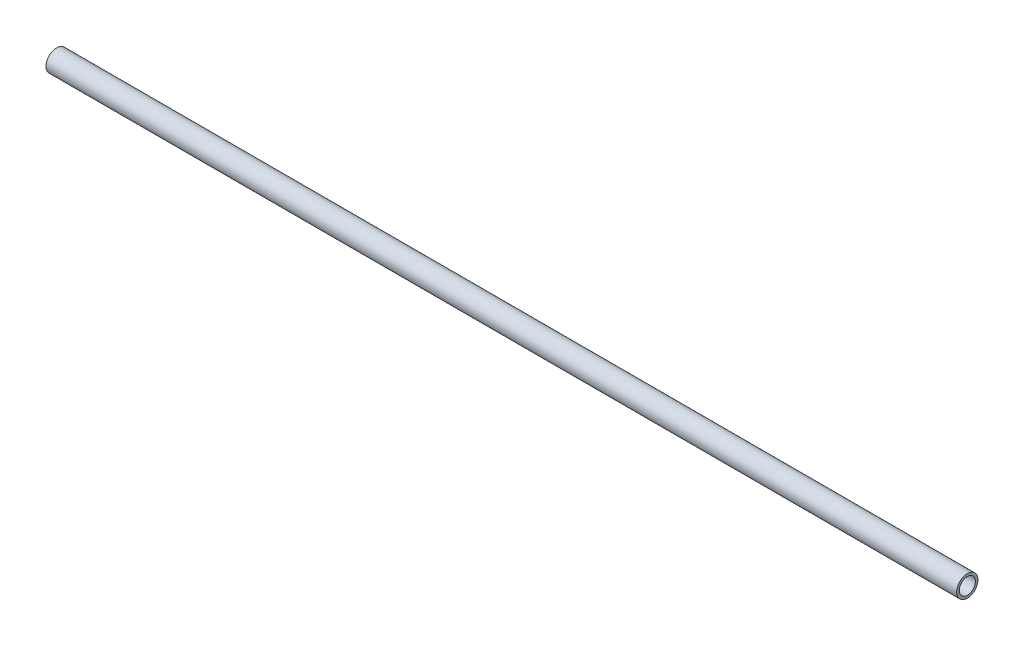
SolidWorks part; units mm, degrees
ref_plane "Front Plane" through (0, 0, 0) normal (0, 0, 1) x (1, 0, 0)
ref_plane "Top Plane" through (0, 0, 0) normal (0, 1, 0) x (1, 0, 0)
ref_plane "Right Plane" through (0, 0, 0) normal (1, 0, 0) x (0, 0, -1)
ref_axis "Axis1" through (-4.5, 0, 0) along (1, 0, 0)
sketch "Sketch1" plane through (0, 0, 0) normal (1, 0, 0) x (0, 0, -1)
  circle A0 centre (0, 0) radius 0.8001
  circle A1 centre (0, 0) radius 1.0541
  dimension "D1" = 1.6002
  dimension "D2" = 2.1082
extrude "Boss-Extrude1" add sketch "Sketch1" along normal blind 90
sketch "Sketch2" plane through (0, 0, 0) normal (-1, 0, 0) x (0, 0, 1)
  line L0 (0, 0) -> (0, 0.6106) construction
  line L2 (-0.304, 0.6106) -> (-0.304, 1.0992)
  line L3 (-0.304, 1.0992) -> (0.304, 1.0992)
  line L4 (0.304, 1.0992) -> (0.304, 0.6106)
  arc A0 (-0.304, 0.6106) -> (0.304, 0.6106) centre (0, 0.6106) ccw
  dimension "D1" = 0.608
extrude "Cut-Extrude1" [suppressed] cut sketch "Sketch2" against normal blind 1
sketch "Sketch3" plane through (0, 0, 0) normal (0, 0, 1) x (1, 0, 0)
  line L0 (1.0797, 0) -> (2.5797, 0) construction
  line L1 (1.0797, 0.3969) -> (2.5797, 0.3969)
  line L2 (1.0797, -0.3969) -> (2.5797, -0.3969)
  arc A0 (1.0797, 0.3969) -> (1.0797, -0.3969) centre (1.0797, 0) ccw
  arc A1 (2.5797, -0.3969) -> (2.5797, 0.3969) centre (2.5797, 0) ccw
  point P3 (1.8297, 0)
  dimension "D1" = 0.3969
  dimension "D2" = 1.5
extrude "Cut-Extrude2" cut sketch "Sketch3" against normal blind 10
equation "\"Do\"=8.5mm"
equation "\"Lo\"=10"
equation "\"screw_diam\" = 3.5mm"
equation "\"wheel_Do\"=12.5mm"
equation "\"wheel_thickness\"=4mm"
equation "\"Collet_diameter\"=4.3"
equation "\"clearance\"= 0.5mm"
equation "\"handle_body_width\" = 10mm"
equation "\"finger_diameter\"=35"
equation "\"collet_lid_diameter\"=10"
equation "\"screw_cap_diam\"=5.15"
equation "\"handle_thickness\"=12.5mm"
equation "\"post_hole_diam\"=2"
equation "\"roll_rod_diam\"= 6.5 "
equation "\"roll_rod_length\"=6.6"
equation "\"disc_diam\"=5"
equation "\"disc_width\"=1.5"
equation "\"arm_width\"=5"
equation "\"arm_thickness\"=4.5"
equation "\"wheel_total_diam\"=30"
equation "\"spring_diam\"=4.1"
equation "\"collet_length\" = 18.75mm"
equation "\"tip_length\" = 40mm"
equation "\"cable_tube_OD\"=0.508"
equation "\"D1@Sketch2\"=\"cable_tube_OD\"+0.1"
